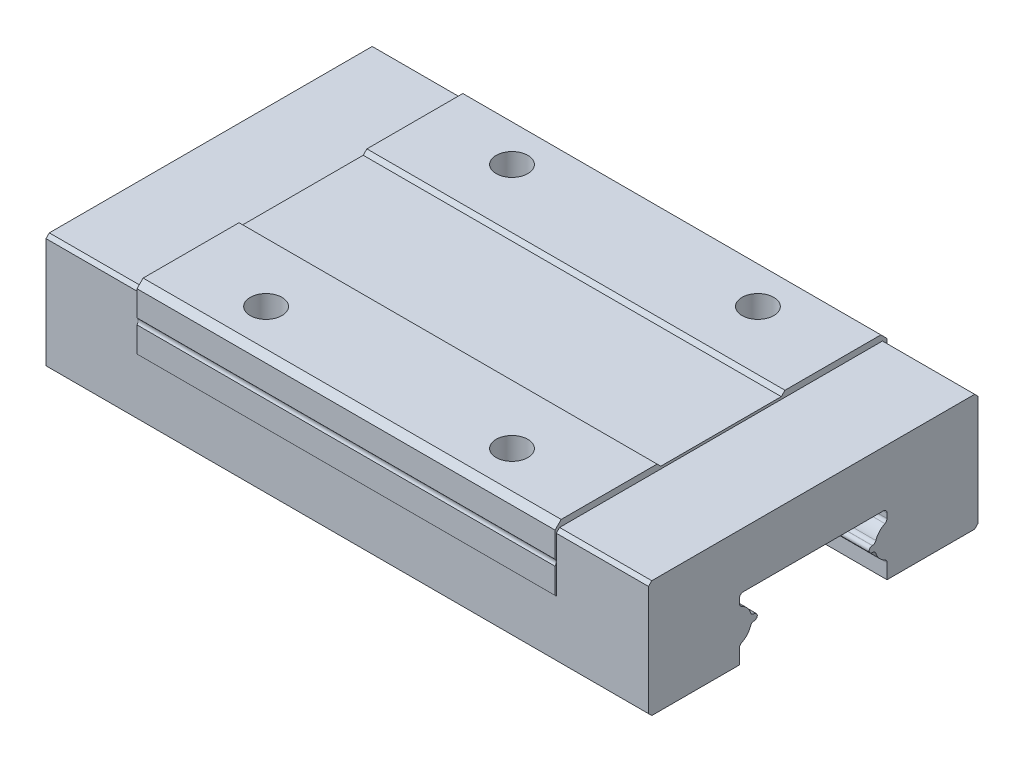
SolidWorks part; units mm, degrees
ref_plane "前视基准面" through (0, 0, 0) normal (0, 0, 1) x (1, 0, 0)
ref_plane "上视基准面" through (0, 0, 0) normal (0, 1, 0) x (1, 0, 0)
ref_plane "右视基准面" through (0, 0, 0) normal (1, 0, 0) x (0, 0, -1)
other "Configuration Table"
ref_plane "基准面1" through (-24.5, 0, 0) normal (-1, 0, 0) x (0, -1, 0)
sketch "草图1" plane through (-24.5, 0, 0) normal (-1, 0, 0) x (0, -1, 0)
  line L0 (1, 13.4) -> (-8.5, 13.4)
  line L1 (-8.5, 13.4) -> (-8.5, -13.4)
  line L2 (-8.5, -13.4) -> (1, -13.4)
  line L3 (1, -13.4) -> (1, -6)
  line L4 (1, -6) -> (-0.4089, -6)
  line L5 (-1.51, -5.04) -> (-1.51, -4.8)
  line L6 (-2.01, -4.8) -> (-2.01, -5.04)
  line L7 (-3.1111, -6) -> (-4, -6)
  line L8 (-4, -6) -> (-4, 6)
  line L9 (-4, 6) -> (-3.1111, 6)
  line L10 (-2.01, 5.04) -> (-2.01, 4.8)
  line L11 (-1.51, 4.8) -> (-1.51, 5.04)
  line L12 (-0.4089, 6) -> (1, 6)
  line L13 (1, 6) -> (1, 13.4)
  arc A0 (-0.4089, -6) -> (-1.51, -5.04) centre (-1.76, -6.4382) ccw
  arc A1 (-1.51, -4.8) -> (-2.01, -4.8) centre (-1.76, -4.8) ccw
  arc A2 (-2.01, -5.04) -> (-3.1111, -6) centre (-1.76, -6.4382) ccw
  arc A3 (-3.1111, 6) -> (-2.01, 5.04) centre (-1.76, 6.4382) ccw
  arc A4 (-2.01, 4.8) -> (-1.51, 4.8) centre (-1.76, 4.8) ccw
  arc A5 (-1.51, 5.04) -> (-0.4089, 6) centre (-1.76, 6.4382) ccw
extrude "凸台-拉伸1" add sketch "草图1" against normal blind 49
sketch "草图2" plane through (0, 0, -13.4) normal (0, 0, -1) x (-1, 0, 0)
  line L0 (17, 8.5) -> (17, 3.8)
  line L1 (17, 3.8) -> (-17, 3.8)
  line L2 (-17, 3.8) -> (-17, 8.5)
  line L3 (-17, 8.5) -> (17, 8.5)
extrude "凸台-拉伸2" add sketch "草图2" along normal blind 0.1
sketch "草图3" plane through (0, 0, 13.4) normal (0, 0, 1) x (1, 0, 0)
  line L0 (17, 8.5) -> (17, 3.9)
  line L1 (17, 3.9) -> (-17, 3.9)
  line L2 (-17, 3.9) -> (-17, 8.5)
  line L3 (-17, 8.5) -> (17, 8.5)
extrude "凸台-拉伸3" add sketch "草图3" along normal blind 0.1
sketch "草图4" plane through (0, 8.5, 0) normal (0, 1, 0) x (-1, 0, 0)
  line L0 (17, 13.5) -> (17, -13.5)
  line L1 (17, -13.5) -> (-17, -13.5)
  line L2 (-17, -13.5) -> (-17, 13.5)
  line L3 (-17, 13.5) -> (17, 13.5)
extrude "凸台-拉伸4" add sketch "草图4" along normal blind 0.5
sketch "草图5" plane through (17, 0, 0) normal (1, 0, 0) x (0, 0, -1)
  line L0 (-13.5, 6.4449) -> (-13.5, 5.9551)
  arc A0 (-13.5, 5.9551) -> (-13.5, 6.4449) centre (-13.75, 6.2) ccw
extrude "切除-拉伸1" cut sketch "草图5" against normal blind 34
sketch "草图6" plane through (17, 0, 0) normal (1, 0, 0) x (0, 0, -1)
  line L0 (4.9, 9) -> (-4.9, 9)
  line L1 (-4.9, 9) -> (-4.9, 8.7)
  line L2 (-4.9, 8.7) -> (4.9, 8.7)
  line L3 (4.9, 8.7) -> (4.9, 9)
extrude "切除-拉伸2" cut sketch "草图6" against normal through all
draft "拔模1" type of draft neutral plane draft angle 45 faces to draft 1 face at (0, 3.9, 13.45) neutral plane through (0, 0, 13.5) neutral plane normal (0, 0, 1) parameters "D1"=45
draft "拔模2" type of draft neutral plane draft angle 45 faces to draft 1 face at (0, 3.8, -13.45) neutral plane through (24.5, 8.5, -13.4) neutral plane normal (0, 0, -1) parameters "D1"=45
draft "拔模3" type of draft neutral plane draft angle 45 faces to draft 2 face at (0, 8.85, 4.9) face at (0, 8.85, -4.9) neutral plane through (-24.5, 8.7, 4.9) neutral plane normal (0, 1, 0) parameters "D1"=45
hole_wizard "M2 间隙孔1" positions "草图8" profile "草图7" hole size "M2" standard "ANSI Metric"
sketch "草图8" plane through (0, 9, 0) normal (0, 1, 0) x (1, 0, 0)
  point P0 (10, -10)
  point P1 (-10, -10)
  point P2 (-10, 10)
  point P3 (10, 10)
sketch "草图7" plane through (10, 9, 10) normal (1, 0, 0) x (0, 0, 1)
  line L0 (0, 0) -> (0, 4.2751)
  line L1 (0, 4.2751) -> (1.29, 3.5)
  line L2 (1.29, 3.5) -> (1.29, 0)
  line L5 (1.29, 0) -> (0, 0)
  line L10 (0, 4.2751) -> (-1.29, 3.5) construction
  line L11 (0, -6.35) -> (0, 107.95) construction
  dimension "孔直径" = 2.58
  dimension "孔深度" = 3.5
  dimension "导头角度" = 118
chamfer "倒角1" distance 0.27 angle 45 6 edges at (0, -1, -13.4) (-20.75, 8.5, -13.4) (0, -1, 13.4) (-20.75, 8.5, 13.4) (20.75, 8.5, -13.4) (20.75, 8.5, 13.4)
chamfer "倒角2" distance 0.5 angle 45 2 edges at (0, 9, -13.5) (0, 9, 13.5)
fillet "圆角1" radius 0.3 10 edges at (0, 0.4089, -6) (0, 0.4089, 6) (0, 2.01, -5.04) (0, 4, 6) (0, 3.1111, -6) (0, 3.1111, 6) (0, 1.51, -5.04) (0, 2.01, 5.04) (0, 1.51, 5.04) (0, 4, -6) tangent propagation no
ref_plane "基准面2" through (0, 0, 0) normal (1, 0, 0) x (0, 0, -1)
ref_plane "基准面3" through (0, 0, 0) normal (0, 0, -1) x (-1, 0, 0)
